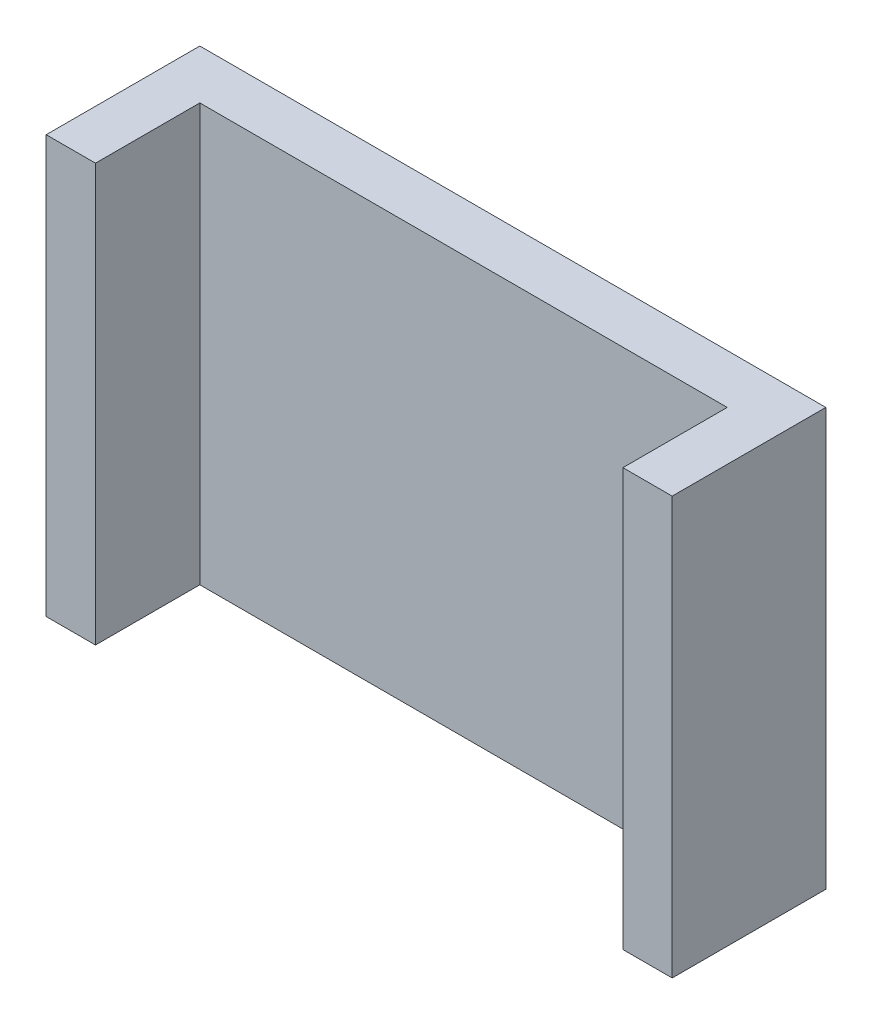
SolidWorks part; units mm, degrees
ref_plane "Front Plane" through (0, 0, 0) normal (0, 0, 1) x (1, 0, 0)
ref_plane "Top Plane" through (0, 0, 0) normal (0, 1, 0) x (1, 0, 0)
ref_plane "Right Plane" through (0, 0, 0) normal (1, 0, 0) x (0, 0, -1)
sketch "Sketch3" plane through (0, 0, 0) normal (0, 1, 0) x (1, 0, 0)
  line L0 (0, -3) -> (0, 3) construction
  line L1 (-38.1, -3) -> (38.1, -3)
  line L2 (-38.1, -3) -> (-38.1, 3)
  line L3 (-38.1, 3) -> (38.1, 3)
  line L4 (38.1, -3) -> (38.1, 3)
  line L5 (-38.1, -3) -> (38.1, 3) construction
  line L6 (-38.1, 3) -> (38.1, -3) construction
  line L7 (-38.1, -3) -> (-32.1, -3)
  line L8 (-38.1, -3) -> (-38.1, -15.7)
  line L9 (-38.1, -15.7) -> (-32.1, -15.7)
  line L10 (-32.1, -3) -> (-32.1, -15.7)
  line L11 (38.1, -15.7) -> (32.1, -15.7)
  line L12 (32.1, -3) -> (32.1, -15.7)
  line L13 (38.1, -3) -> (32.1, -3)
  line L14 (38.1, -3) -> (38.1, -15.7)
  point P0 (0, 0)
  dimension "D1" = 76.2
  dimension "D2" = 6
  dimension "D3" = 12.7
  dimension "D4" = 6
extrude "Boss-Extrude1" add sketch "Sketch3" along normal blind 50.8 contours L10 L1 L8 L9 | L1 L4 L3 L2 | L14 L1 L12 L11 region at (0, 0, 0) region at (-35.1, 0, 9.35) region at (35.1, 0, 9.35)
